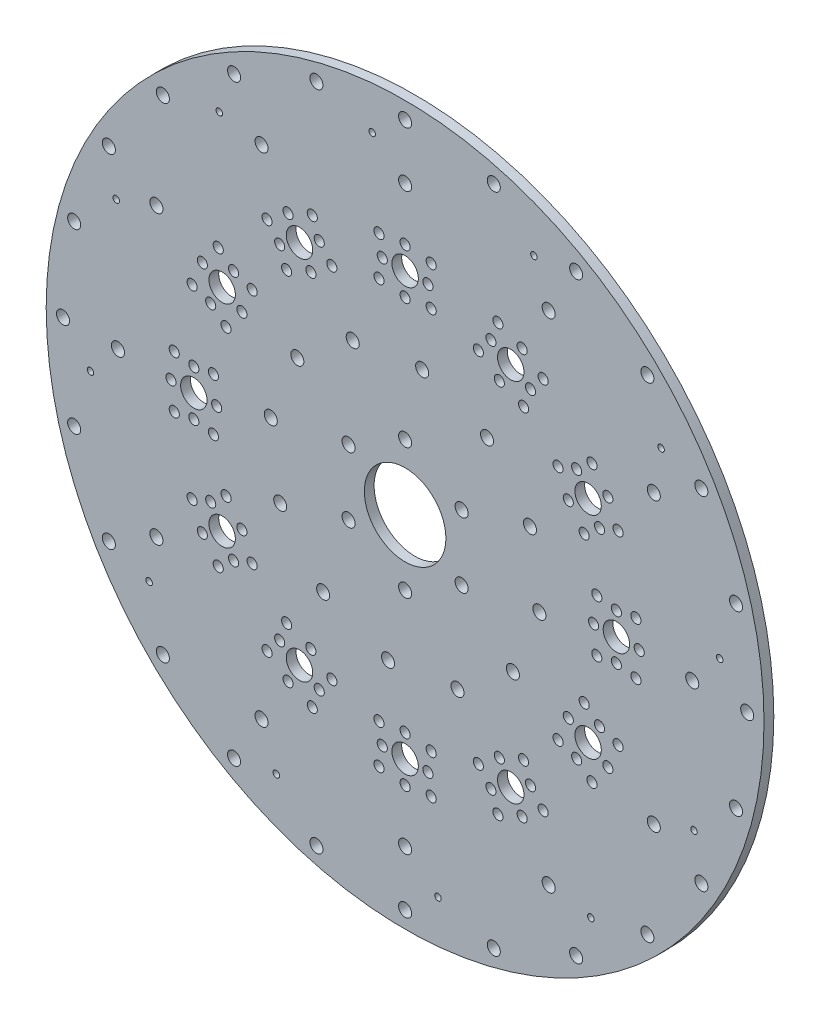
SolidWorks part; units mm, degrees
ref_plane "前视基准面" through (0, 0, 0) normal (0, 0, 1) x (1, 0, 0)
ref_plane "上视基准面" through (0, 0, 0) normal (0, 1, 0) x (1, 0, 0)
ref_plane "右视基准面" through (0, 0, 0) normal (1, 0, 0) x (0, 0, -1)
other "Configuration Table"
sketch "草图1" plane through (0, 0, 0) normal (0, 0, 1) x (1, 0, 0)
  line L0 (-12.5, 46.6506) -> (-12.5, 82.8506) construction
  line L13 (28.4471, 65.2718) -> (36.3035, 46.8795) construction
  line L15 (0, 0) -> (10, 0)
  line L19 (-8, 70.7506) -> (8, 58.7506) construction
  line L20 (-8, 58.7506) -> (8, 70.7506) construction
  line L21 (22.4471, 54.8795) -> (42.3035, 57.2718) construction
  line L22 (57.2718, 42.3035) -> (54.8795, 22.4471) construction
  line L23 (46.8795, 36.3035) -> (65.2718, 28.4471) construction
  line L24 (70.7506, 8) -> (58.7506, -8) construction
  line L25 (58.7506, 8) -> (70.7506, -8) construction
  line L26 (65.2718, -28.4471) -> (46.8795, -36.3035) construction
  line L27 (54.8795, -22.4471) -> (57.2718, -42.3035) construction
  line L28 (42.3035, -57.2718) -> (22.4471, -54.8795) construction
  line L29 (36.3035, -46.8795) -> (28.4471, -65.2718) construction
  line L30 (8, -70.7506) -> (-8, -58.7506) construction
  line L31 (8, -58.7506) -> (-8, -70.7506) construction
  line L32 (-28.4471, -65.2718) -> (-36.3035, -46.8795) construction
  line L33 (-22.4471, -54.8795) -> (-42.3035, -57.2718) construction
  line L34 (-57.2718, -42.3035) -> (-54.8795, -22.4471) construction
  line L35 (-46.8795, -36.3035) -> (-65.2718, -28.4471) construction
  line L36 (-70.7506, -8) -> (-58.7506, 8) construction
  line L37 (-58.7506, -8) -> (-70.7506, 8) construction
  line L38 (-65.2718, 28.4471) -> (-46.8795, 36.3035) construction
  line L39 (-54.8795, 22.4471) -> (-57.2718, 42.3035) construction
  line L40 (-42.3035, 57.2718) -> (-22.4471, 54.8795) construction
  line L41 (-36.3035, 46.8795) -> (-28.4471, 65.2718) construction
  line L42 (0, 0) -> (-8, 58.7506) construction
  line L43 (12.5, 46.6506) -> (-12.5, 46.6506) construction
  line L44 (-12.5, 46.6506) -> (-34.1506, 34.1506) construction
  line L45 (-34.1506, 34.1506) -> (-46.6506, 12.5) construction
  line L46 (-46.6506, 12.5) -> (-46.6506, -12.5) construction
  line L47 (-46.6506, -12.5) -> (-34.1506, -34.1506) construction
  line L48 (-34.1506, -34.1506) -> (-12.5, -46.6506) construction
  line L49 (-12.5, -46.6506) -> (12.5, -46.6506) construction
  line L50 (12.5, -46.6506) -> (34.1506, -34.1506) construction
  line L51 (34.1506, -34.1506) -> (46.6506, -12.5) construction
  line L52 (46.6506, -12.5) -> (46.6506, 12.5) construction
  line L53 (46.6506, 12.5) -> (34.1506, 34.1506) construction
  line L54 (34.1506, 34.1506) -> (12.5, 46.6506) construction
  line L55 (0, 0) -> (-36.3035, 46.8795) construction
  line L56 (0, 110) -> (0, 104.84) construction
  line L57 (0, 110) -> (0, 88) construction
  line L58 (0, 104.84) -> (0, 88) construction
  line L59 (0, 0) -> (-16.0513, 38.2702) construction
  line L60 (0, 96.42) -> (-10.08, 96.42) construction
  line L61 (0, 0) -> (0, 20) construction
  line L63 (0, 0) -> (-27.176, -101.4222) construction
  circle A0 centre (0, 64.7506) radius 4.05
  circle A3 centre (0, 64.7506) radius 7 construction
  circle A4 centre (0, 71.7506) radius 1.55
  circle A5 centre (7, 64.7506) radius 1.55
  circle A6 centre (0, 57.7506) radius 1.55
  circle A7 centre (-7, 64.7506) radius 1.55
  circle A8 centre (-8, 70.7506) radius 1.55
  circle A9 centre (8, 70.7506) radius 1.55
  circle A10 centre (-8, 58.7506) radius 1.55
  circle A11 centre (8, 58.7506) radius 1.55
  circle A12 centre (32.3753, 56.0757) radius 4.05
  circle A13 centre (35.8753, 62.1379) radius 1.55
  circle A14 centre (38.4375, 52.5757) radius 1.55
  circle A15 centre (28.8753, 50.0135) radius 1.55
  circle A16 centre (26.3131, 59.5757) radius 1.55
  circle A17 centre (28.4471, 65.2718) radius 1.55
  circle A18 centre (42.3035, 57.2718) radius 1.55
  circle A19 centre (22.4471, 54.8795) radius 1.55
  circle A20 centre (36.3035, 46.8795) radius 1.55
  circle A21 centre (32.3753, 56.0757) radius 7 construction
  circle A22 centre (56.0757, 32.3753) radius 4.05
  circle A23 centre (62.1379, 35.8753) radius 1.55
  circle A24 centre (59.5757, 26.3131) radius 1.55
  circle A25 centre (50.0135, 28.8753) radius 1.55
  circle A26 centre (52.5757, 38.4375) radius 1.55
  circle A27 centre (57.2718, 42.3035) radius 1.55
  circle A28 centre (65.2718, 28.4471) radius 1.55
  circle A29 centre (46.8795, 36.3035) radius 1.55
  circle A30 centre (54.8795, 22.4471) radius 1.55
  circle A31 centre (56.0757, 32.3753) radius 7 construction
  circle A32 centre (64.7506, 0) radius 4.05
  circle A33 centre (71.7506, 0) radius 1.55
  circle A34 centre (64.7506, -7) radius 1.55
  circle A35 centre (57.7506, 0) radius 1.55
  circle A36 centre (64.7506, 7) radius 1.55
  circle A37 centre (70.7506, 8) radius 1.55
  circle A38 centre (70.7506, -8) radius 1.55
  circle A39 centre (58.7506, 8) radius 1.55
  circle A40 centre (58.7506, -8) radius 1.55
  circle A41 centre (64.7506, 0) radius 7 construction
  circle A42 centre (56.0757, -32.3753) radius 4.05
  circle A43 centre (62.1379, -35.8753) radius 1.55
  circle A44 centre (52.5757, -38.4375) radius 1.55
  circle A45 centre (50.0135, -28.8753) radius 1.55
  circle A46 centre (59.5757, -26.3131) radius 1.55
  circle A47 centre (65.2718, -28.4471) radius 1.55
  circle A48 centre (57.2718, -42.3035) radius 1.55
  circle A49 centre (54.8795, -22.4471) radius 1.55
  circle A50 centre (46.8795, -36.3035) radius 1.55
  circle A51 centre (56.0757, -32.3753) radius 7 construction
  circle A52 centre (32.3753, -56.0757) radius 4.05
  circle A53 centre (35.8753, -62.1379) radius 1.55
  circle A54 centre (26.3131, -59.5757) radius 1.55
  circle A55 centre (28.8753, -50.0135) radius 1.55
  circle A56 centre (38.4375, -52.5757) radius 1.55
  circle A57 centre (42.3035, -57.2718) radius 1.55
  circle A58 centre (28.4471, -65.2718) radius 1.55
  circle A59 centre (36.3035, -46.8795) radius 1.55
  circle A60 centre (22.4471, -54.8795) radius 1.55
  circle A61 centre (32.3753, -56.0757) radius 7 construction
  circle A62 centre (0, -64.7506) radius 4.05
  circle A63 centre (0, -71.7506) radius 1.55
  circle A64 centre (-7, -64.7506) radius 1.55
  circle A65 centre (0, -57.7506) radius 1.55
  circle A66 centre (7, -64.7506) radius 1.55
  circle A67 centre (8, -70.7506) radius 1.55
  circle A68 centre (-8, -70.7506) radius 1.55
  circle A69 centre (8, -58.7506) radius 1.55
  circle A70 centre (-8, -58.7506) radius 1.55
  circle A71 centre (0, -64.7506) radius 7 construction
  circle A72 centre (-32.3753, -56.0757) radius 4.05
  circle A73 centre (-35.8753, -62.1379) radius 1.55
  circle A74 centre (-38.4375, -52.5757) radius 1.55
  circle A75 centre (-28.8753, -50.0135) radius 1.55
  circle A76 centre (-26.3131, -59.5757) radius 1.55
  circle A77 centre (-28.4471, -65.2718) radius 1.55
  circle A78 centre (-42.3035, -57.2718) radius 1.55
  circle A79 centre (-22.4471, -54.8795) radius 1.55
  circle A80 centre (-36.3035, -46.8795) radius 1.55
  circle A81 centre (-32.3753, -56.0757) radius 7 construction
  circle A82 centre (-56.0757, -32.3753) radius 4.05
  circle A83 centre (-62.1379, -35.8753) radius 1.55
  circle A84 centre (-59.5757, -26.3131) radius 1.55
  circle A85 centre (-50.0135, -28.8753) radius 1.55
  circle A86 centre (-52.5757, -38.4375) radius 1.55
  circle A87 centre (-57.2718, -42.3035) radius 1.55
  circle A88 centre (-65.2718, -28.4471) radius 1.55
  circle A89 centre (-46.8795, -36.3035) radius 1.55
  circle A90 centre (-54.8795, -22.4471) radius 1.55
  circle A91 centre (-56.0757, -32.3753) radius 7 construction
  circle A92 centre (-64.7506, 0) radius 4.05
  circle A93 centre (-71.7506, 0) radius 1.55
  circle A94 centre (-64.7506, 7) radius 1.55
  circle A95 centre (-57.7506, 0) radius 1.55
  circle A96 centre (-64.7506, -7) radius 1.55
  circle A97 centre (-70.7506, -8) radius 1.55
  circle A98 centre (-70.7506, 8) radius 1.55
  circle A99 centre (-58.7506, -8) radius 1.55
  circle A100 centre (-58.7506, 8) radius 1.55
  circle A101 centre (-64.7506, 0) radius 7 construction
  circle A102 centre (-56.0757, 32.3753) radius 4.05
  circle A103 centre (-62.1379, 35.8753) radius 1.55
  circle A104 centre (-52.5757, 38.4375) radius 1.55
  circle A105 centre (-50.0135, 28.8753) radius 1.55
  circle A106 centre (-59.5757, 26.3131) radius 1.55
  circle A107 centre (-65.2718, 28.4471) radius 1.55
  circle A108 centre (-57.2718, 42.3035) radius 1.55
  circle A109 centre (-54.8795, 22.4471) radius 1.55
  circle A110 centre (-46.8795, 36.3035) radius 1.55
  circle A111 centre (-56.0757, 32.3753) radius 7 construction
  circle A112 centre (-32.3753, 56.0757) radius 4.05
  circle A113 centre (-35.8753, 62.1379) radius 1.55
  circle A114 centre (-26.3131, 59.5757) radius 1.55
  circle A115 centre (-28.8753, 50.0135) radius 1.55
  circle A116 centre (-38.4375, 52.5757) radius 1.55
  circle A117 centre (-42.3035, 57.2718) radius 1.55
  circle A118 centre (-28.4471, 65.2718) radius 1.55
  circle A119 centre (-36.3035, 46.8795) radius 1.55
  circle A120 centre (-22.4471, 54.8795) radius 1.55
  circle A121 centre (-32.3753, 56.0757) radius 7 construction
  circle A122 centre (0, 0) radius 46.6506 construction
  circle A124 centre (-16.0513, 38.2702) radius 2
  circle A125 centre (5.2342, 41.1686) radius 2
  circle A126 centre (25.1173, 33.0359) radius 2
  circle A127 centre (38.2702, 16.0513) radius 2
  circle A128 centre (41.1686, -5.2342) radius 2
  circle A129 centre (33.0359, -25.1173) radius 2
  circle A130 centre (16.0513, -38.2702) radius 2
  circle A131 centre (-5.2342, -41.1686) radius 2
  circle A132 centre (-25.1173, -33.0359) radius 2
  circle A133 centre (-38.2702, -16.0513) radius 2
  circle A134 centre (-41.1686, 5.2342) radius 2
  circle A135 centre (-33.0359, 25.1173) radius 2
  circle A136 centre (0, 0) radius 110
  circle A137 centre (0, 104.84) radius 2
  circle A138 centre (0, 88) radius 2
  circle A139 centre (52.42, 90.7941) radius 2
  circle A140 centre (44, 76.2102) radius 2
  circle A141 centre (90.7941, 52.42) radius 2
  circle A142 centre (76.2102, 44) radius 2
  circle A143 centre (104.84, 0) radius 2
  circle A144 centre (88, 0) radius 2
  circle A145 centre (90.7941, -52.42) radius 2
  circle A146 centre (76.2102, -44) radius 2
  circle A147 centre (52.42, -90.7941) radius 2
  circle A148 centre (44, -76.2102) radius 2
  circle A149 centre (0, -104.84) radius 2
  circle A150 centre (0, -88) radius 2
  circle A151 centre (-52.42, -90.7941) radius 2
  circle A152 centre (-44, -76.2102) radius 2
  circle A153 centre (-90.7941, -52.42) radius 2
  circle A154 centre (-76.2102, -44) radius 2
  circle A155 centre (-104.84, 0) radius 2
  circle A156 centre (-88, 0) radius 2
  circle A157 centre (-90.7941, 52.42) radius 2
  circle A158 centre (-76.2102, 44) radius 2
  circle A159 centre (-52.42, 90.7941) radius 2
  circle A160 centre (-44, 76.2102) radius 2
  circle A161 centre (-10.08, 96.42) radius 1
  circle A162 centre (39.4805, 88.5422) radius 1
  circle A163 centre (78.4622, 56.9395) radius 1
  circle A164 centre (96.42, 10.08) radius 1
  circle A165 centre (88.5422, -39.4805) radius 1
  circle A166 centre (56.9395, -78.4622) radius 1
  circle A167 centre (10.08, -96.42) radius 1
  circle A168 centre (-39.4805, -88.5422) radius 1
  circle A169 centre (-78.4622, -56.9395) radius 1
  circle A170 centre (-96.42, -10.08) radius 1
  circle A171 centre (-88.5422, 39.4805) radius 1
  circle A172 centre (-56.9395, 78.4622) radius 1
  circle A173 centre (0, 0) radius 12.5
  circle A174 centre (0, 20) radius 2
  circle A175 centre (17.3205, 10) radius 2
  circle A176 centre (17.3205, -10) radius 2
  circle A177 centre (0, -20) radius 2
  circle A178 centre (-17.3205, -10) radius 2
  circle A179 centre (-17.3205, 10) radius 2
  circle A180 centre (-27.176, -101.4222) radius 2
  circle A181 centre (-74.2462, -74.2462) radius 2
  circle A182 centre (-101.4222, -27.176) radius 2
  circle A183 centre (-101.4222, 27.176) radius 2
  circle A184 centre (-74.2462, 74.2462) radius 2
  circle A185 centre (-27.176, 101.4222) radius 2
  circle A186 centre (27.176, 101.4222) radius 2
  circle A187 centre (74.2462, 74.2462) radius 2
  circle A188 centre (101.4222, 27.176) radius 2
  circle A189 centre (101.4222, -27.176) radius 2
  circle A190 centre (74.2462, -74.2462) radius 2
  circle A191 centre (27.176, -101.4222) radius 2
  point P276 (0, 0)
  point P325 (0, 0)
  point P351 (0, 0)
  point P362 (0, 0)
  point P388 (0, 0)
  dimension "D2" = 36.2
  dimension "D3" = 10
  dimension "D4" = 8.1
  dimension "D5" = 14
  dimension "D6" = 3.1
  dimension "D9" = 3.1
  dimension "D10" = 3.1
  dimension "D11" = 3.1
  dimension "D12" = 3.1
  dimension "D13" = 4
  dimension "D14" = 220
  dimension "D17" = 4
  dimension "D18" = 4
  dimension "D20" = 2
  dimension "D21" = 25
  dimension "D23" = 4
  dimension "D26" = 4
  dimension "D7" = 12
  dimension "D8" = 16
  dimension "D15" = 5.16
  dimension "D16" = 22
  dimension "D19" = 10.08
  dimension "D22" = 20
  dimension "D25" = 105
  dimension "D27" = 12
  dimension "D24" = 6
  dimension "D28" = 12
extrude "凸台-拉伸1" add sketch "草图1" along normal blind 3 contours A135 A134 A133 A132 A131 A130 A129 A128 A127 A126 A125 A124 A120 A119 A118 A117 A116 A115 A114 A113 A112 A110 A109 A108 A107 region at (-106.8887, 0, 0)
ref_axis "基准轴1" through (0, 0, 3) along (0, 0, -1)
